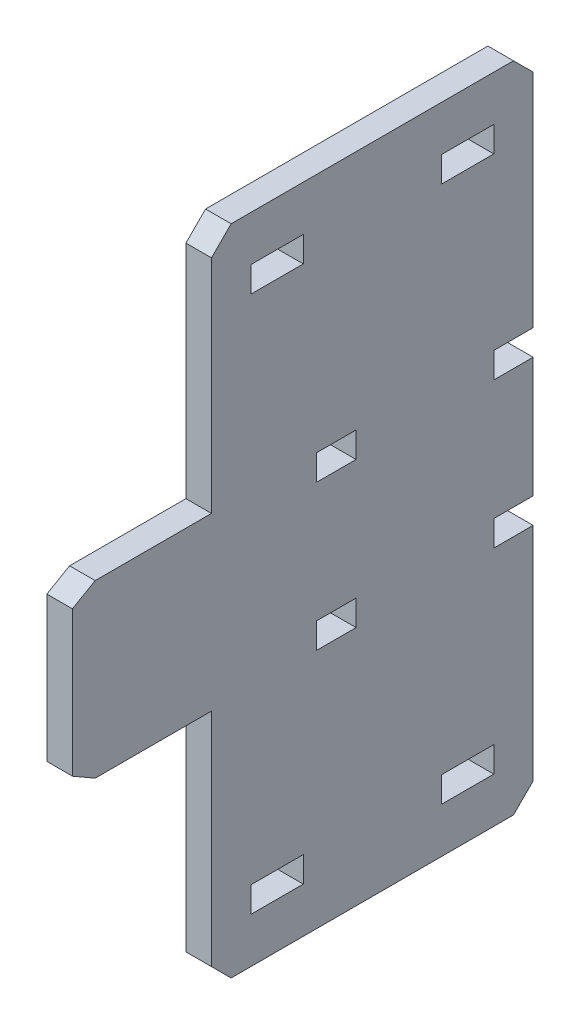
SolidWorks part; units mm, degrees
ref_plane "Front" through (0, 0, 0) normal (0, 0, 1) x (1, 0, 0)
ref_plane "Top" through (0, 0, 0) normal (0, 1, 0) x (1, 0, 0)
ref_plane "Right" through (0, 0, 0) normal (1, 0, 0) x (0, 0, -1)
ref_axis "side-side" through (80.9, 0, 0) along (-1, 0, 0)
ref_axis "up-down" through (0, 50, 0) along (0, -1, 0)
ref_axis "front-back" through (0, 0, -80.9) along (0, 0, 1)
sketch "Sketch1" plane through (0, 0, 0) normal (1, 0, 0) x (0, 0, -1)
  line L0 (27.94, 54.483) -> (27.94, 49.53) construction
  line L1 (38.1, -49.53) -> (27.94, -49.53)
  line L2 (45.72, -63.246) -> (45.72, -16.5735)
  line L3 (38.1, 49.53) -> (27.94, 49.53)
  line L4 (-43.4959, -14.0335) -> (-43.4959, 14.0335)
  line L5 (109.3291, 0) -> (45.72, 0) construction
  line L6 (1.2081, 54.483) -> (1.2081, 49.53) construction
  line L7 (27.94, 54.483) -> (27.94, 49.53)
  line L8 (45.72, -54.61) -> (38.1, -54.61) construction
  line L9 (38.1, 49.53) -> (38.1, 54.483)
  line L10 (38.1, 54.61) -> (45.72, 54.61) construction
  line L11 (38.1, -49.53) -> (38.1, -54.483) construction
  line L12 (-16.5719, 54.61) -> (-8.9519, 54.61) construction
  line L13 (38.1, 16.5735) -> (45.72, 16.5735)
  line L14 (38.1, -54.483) -> (38.1, -49.53)
  line L15 (-8.9519, 54.483) -> (-8.9519, 49.53)
  line L16 (-16.5719, -54.61) -> (-8.9519, -54.61) construction
  line L17 (38.1, 16.5735) -> (38.1, 11.6205)
  line L18 (38.1, 11.6205) -> (45.72, 11.6205)
  line L19 (-8.9519, -54.483) -> (-8.9519, -49.53)
  line L20 (45.72, 16.5735) -> (45.72, 63.246)
  line L21 (38.1, -11.6205) -> (45.72, -11.6205)
  line L22 (38.1, -11.6205) -> (38.1, -16.5735)
  line L23 (38.1, -16.5735) -> (45.72, -16.5735)
  line L24 (1.2081, 54.483) -> (1.2081, 49.53)
  line L25 (11.43, 16.5735) -> (3.81, 16.5735)
  line L26 (11.43, 16.5735) -> (11.43, 11.6205)
  line L27 (11.43, 11.6205) -> (3.81, 11.6205)
  line L28 (3.81, 16.5735) -> (3.81, 11.6205)
  line L29 (3.81, -16.5735) -> (11.43, -16.5735)
  line L30 (3.81, -16.5735) -> (3.81, -11.6205)
  line L31 (3.81, -11.6205) -> (11.43, -11.6205)
  line L32 (11.43, -16.5735) -> (11.43, -11.6205)
  line L33 (-8.9519, -49.53) -> (-8.9519, -54.483) construction
  line L34 (45.72, -11.6205) -> (45.72, 11.6205)
  line L35 (-16.5719, 63.246) -> (-16.5719, 16.5735)
  line L36 (-16.5719, -63.246) -> (-16.5719, -16.5735)
  line L37 (-16.5719, 16.5735) -> (-39.0964, 16.5735)
  line L38 (-16.5719, -16.5735) -> (-39.0964, -16.5735)
  line L39 (-39.0964, 16.5735) -> (-43.4959, 14.0335)
  line L40 (-39.0964, -16.5735) -> (-43.4959, -14.0335)
  line L41 (45.72, 63.246) -> (-16.5719, 63.246)
  line L43 (38.1, 54.483) -> (27.94, 54.483)
  line L45 (38.1, -54.483) -> (27.94, -54.483)
  line L46 (45.72, -63.246) -> (-16.5719, -63.246)
  line L47 (1.2081, 54.483) -> (-8.9519, 54.483)
  line L48 (1.2081, 49.53) -> (-8.9519, 49.53)
  line L49 (27.94, -49.53) -> (27.94, -54.483) construction
  line L50 (1.2081, -49.53) -> (1.2081, -54.483) construction
  line L51 (27.94, -49.53) -> (27.94, -54.483)
  line L52 (1.2081, -49.53) -> (1.2081, -54.483)
  line L53 (1.2081, -49.53) -> (-8.9519, -49.53)
  line L54 (1.2081, -54.483) -> (-8.9519, -54.483)
extrude "Boss-Extrude1" add sketch "Sketch1" along normal mid plane 4.953
chamfer "Chamfer2" distance 3.81 angle 45 4 edges at (0, -63.246, -45.72) (0, -63.246, 16.5719) (0, 63.246, -45.72) (0, 63.246, 16.5719)
